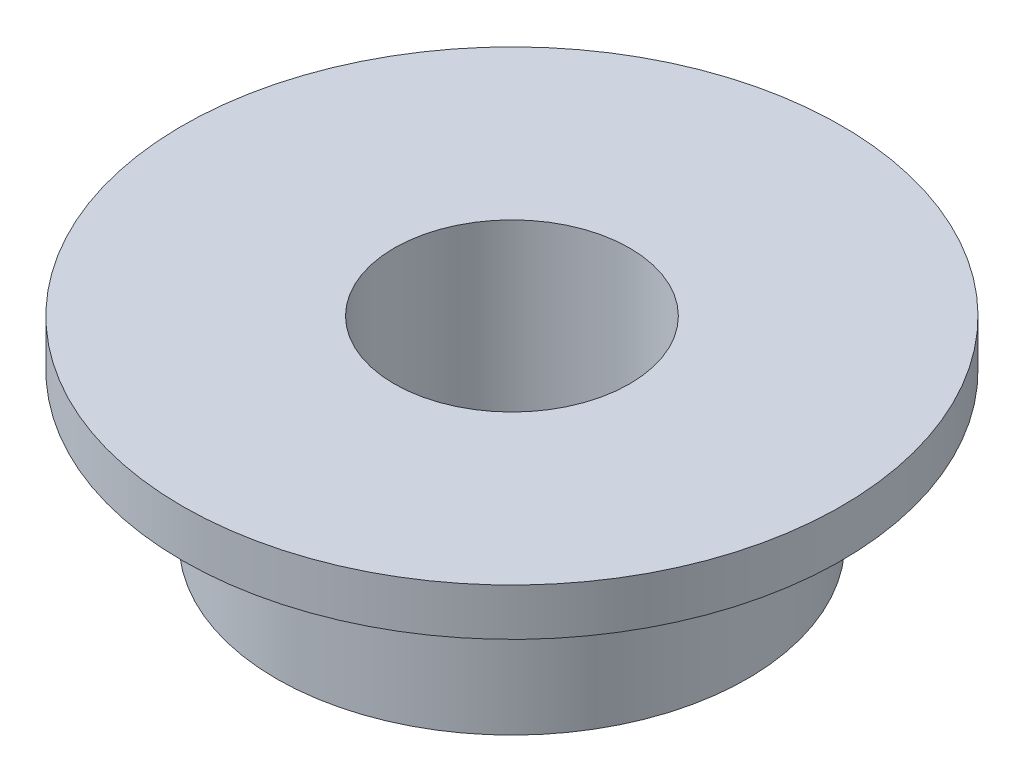
SolidWorks part; units mm, degrees
ref_plane "Front Plane" through (0, 0, 0) normal (0, 0, 1) x (1, 0, 0)
ref_plane "Top Plane" through (0, 0, 0) normal (0, 1, 0) x (1, 0, 0)
ref_plane "Right Plane" through (0, 0, 0) normal (1, 0, 0) x (0, 0, -1)
sketch "Sketch1" plane through (0, 0, 0) normal (0, 1, 0) x (1, 0, 0)
  circle A0 centre (0, 0) radius 5
  circle A1 centre (0, 0) radius 2.5
  circle A2 centre (0, 0) radius 7
  dimension "D1" = 10
  dimension "D2" = 5
  dimension "D3" = 2
extrude "Boss-Extrude1" add sketch "Sketch1" against normal blind 3.175 contours A0 A1 region at (-4.8586, 0, 0)
extrude "Boss-Extrude2" add sketch "Sketch1<3>" along normal blind 1 contours A0 A1 | A2 A0 region at (-4.8586, 0, 0) region at (-6.802, 0, 0)
sketch "Sketch1<3>" plane through (0, 0, 0) normal (0, 1, 0) x (1, 0, 0) same geometry as "Sketch1"
